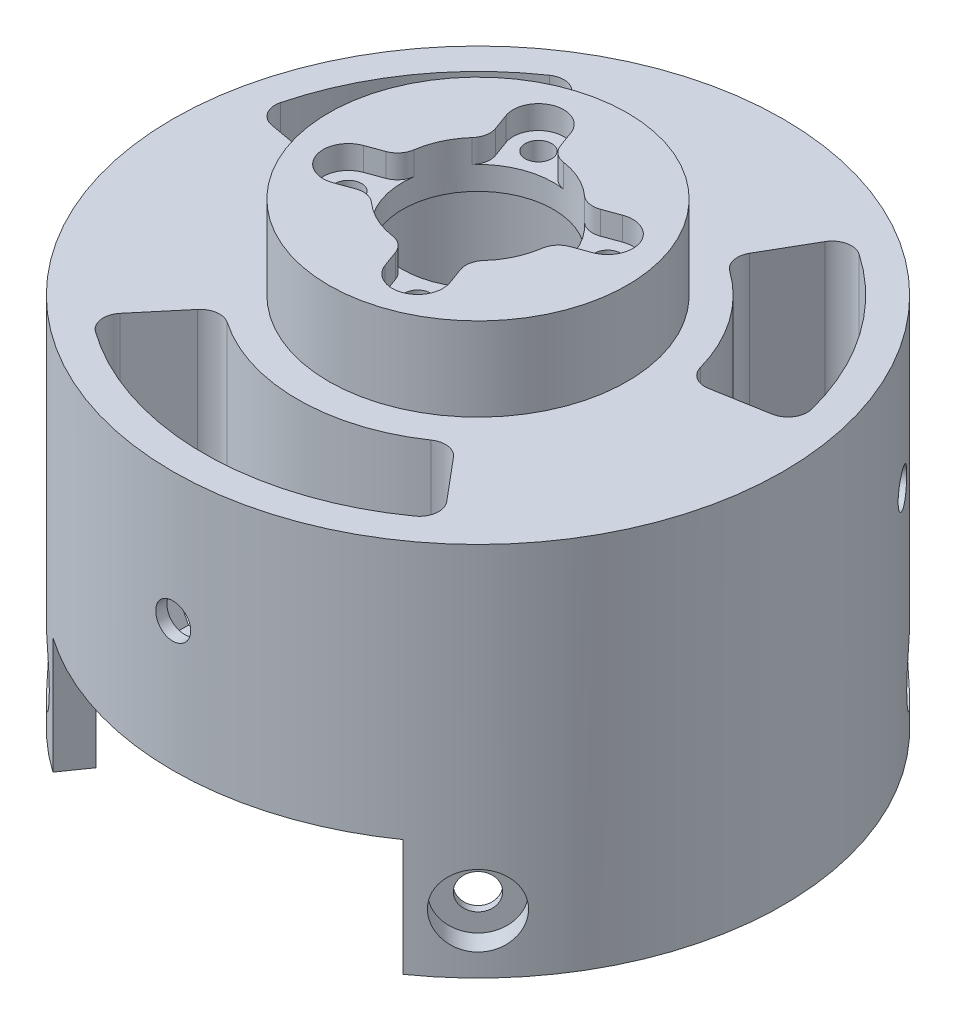
SolidWorks part; units mm, degrees
ref_plane "Front Plane" through (0, 0, 0) normal (0, 0, 1) x (1, 0, 0)
ref_plane "Top Plane" through (0, 0, 0) normal (0, 1, 0) x (1, 0, 0)
ref_plane "Right Plane" through (0, 0, 0) normal (1, 0, 0) x (0, 0, -1)
sketch "Sketch1" plane through (0, 0, 0) normal (0, 1, 0) x (1, 0, 0)
  line L0 (-29.85, 23.9174) -> (-29.85, -23.9174)
  line L1 (29.85, 23.9174) -> (29.85, -23.9174)
  line L2 (-29.85, 0) -> (29.85, 0) construction
  arc A0 (-29.85, -23.9174) -> (29.85, -23.9174) centre (0, 0) ccw
  arc A1 (29.85, 23.9174) -> (-29.85, 23.9174) centre (0, 0) ccw
  point P9 (0, 0)
  dimension "D1" = 59.7
  dimension "D2" = 76.5
extrude "Boss-Extrude1" add sketch "Sketch1" along normal blind 44
sketch "Sketch2" plane through (0, 44, 0) normal (0, 1, 0) x (1, 0, 0)
  line L0 (-4.4463, 12.216) -> (0, 0) construction
  line L1 (0, 13) -> (0, 0) construction
  circle A0 centre (0, 0) radius 13
  point P3 (-4.4463, 12.216)
  dimension "D1" = 26
  dimension "D2" = 20
hole_wizard "CBORE for M3 SHCS1" positions "Sketch2" profile "Sketch3" counterbore size "M3" standard "ANSI Metric" end condition through all
sketch "Sketch3" plane through (-4.4463, 44, -12.216) normal (1, 0, 0) x (0, 0, 1)
  line L0 (0, 0) -> (0, 44)
  line L1 (0, 44) -> (1.7, 44)
  line L3 (1.7, 44) -> (1.7, 3)
  line L4 (1.7, 3) -> (3.25, 3)
  line L5 (3.25, 3) -> (3.25, 0)
  line L7 (3.25, 0) -> (0, 0)
  line L11 (0, -6.35) -> (0, 107.95) construction
  dimension "Thru Hole Dia." = 3.4
  dimension "Thru Hole Depth" = 44
  dimension "C'Bore Dia." = 6.5
  dimension "C'Bore Depth" = 3
ref_axis "Axis1" through (0, 44, 0) along (0, -1, 0)
pattern_circular "CirPattern1" count 4 over 360 about axis through (0, 44, 0) along (0, -1, 0) of "CBORE for M3 SHCS1"
sketch "Sketch4" plane through (0, 0, 0) normal (0, -1, 0) x (1, 0, 0)
  circle A0 centre (0, 0) radius 16.2
  dimension "D1" = 32.4
extrude "Cut-Extrude1" cut sketch "Sketch4" against normal blind 38
sketch "Sketch5" plane through (0, 44, 0) normal (0, 1, 0) x (1, 0, 0)
  circle A0 centre (0, 0) radius 9.7
extrude "Cut-Extrude2" cut sketch "Sketch5" against normal through all
ref_plane "Plane1" through (0, 0, -38.25) normal (0, 0, -1) x (-1, 0, 0)
sketch "Sketch7" plane through (0, 0, 0) normal (0, -1, 0) x (1, 0, 0)
  line L5 (29.85, 23.9174) -> (29.85, -23.9174)
  line L6 (-29.85, 23.9174) -> (-29.85, -23.9174)
  arc A0 (-29.85, -23.9174) -> (29.85, -23.9174) centre (0, 0) ccw construction
  arc A1 (29.85, 23.9174) -> (-29.85, 23.9174) centre (0, 0) ccw construction
  arc A2 (-29.85, -23.9174) -> (29.85, -23.9174) centre (0, 0) ccw
  arc A3 (29.85, 23.9174) -> (-29.85, 23.9174) centre (0, 0) ccw
  circle A4 centre (0, 0) radius 42.1622
  dimension "D1" = 84.3245
extrude "Boss-Extrude2" add sketch "Sketch7" against normal up to surface (44 mm away) up to face at (0, 44, 9.7)
sketch "Sketch9" plane through (0, 0, 0) normal (1, 0, 0) x (0, 0, -1)
  line L0 (-42.1622, 0) -> (-38.3127, 44)
  line L1 (-38.3127, 44) -> (-42.1622, 44)
  line L2 (-42.1622, 44) -> (-42.1622, 0) construction
  line L3 (-42.1622, 44) -> (-42.1622, 0)
  line L4 (0, 0) -> (0, 44) construction
  line L5 (42.1622, 44) -> (-42.1622, 44) construction
  dimension "D1" = 5
revolve "Cut-Revolve2" cut sketch "Sketch9" angle 360 about L4
sketch "Sketch10" plane through (0, 0, 0) normal (1, 0, 0) x (0, 0, -1)
  line L0 (-19.2, 44) -> (-19.2, 33.2871)
  line L1 (38.3127, 44) -> (-38.3127, 44) construction
  line L2 (-19.2, 33.2871) -> (-39.25, 33.2871)
  line L3 (-38.3127, 44) -> (-42.1622, 0) construction
  line L4 (-39.25, 33.2871) -> (-38.3127, 44)
  line L5 (-38.3127, 44) -> (-19.2, 44)
  line L6 (0, 0) -> (0, 44) construction
  line L10 (-42.1622, 0) -> (42.1622, 0) construction
  line L11 (-16.2, 0) -> (16.2, 0) construction
  line L12 (-16.2, 0) -> (16.2, 0) construction
  line L13 (38.3127, 44) -> (-38.3127, 44) construction
  dimension "D1" = 10.7129
  dimension "D2" = 33.2871
  dimension "D3" = 3
revolve "Cut-Revolve3" cut sketch "Sketch10" angle 360 about L6
sketch "Sketch13" plane through (0, 33.2871, 0) normal (0, 1, 0) x (1, 0, 0)
  line L0 (0, -35.25) -> (0, -39.25) construction
  circle A0 centre (0, 0) radius 35.25
  circle A1 centre (0, 0) radius 19.2 construction
  circle A2 centre (0, 0) radius 19.2
  circle A3 centre (0, 0) radius 39.25 construction
  dimension "D1" = 4
extrude "Cut-Extrude3" cut sketch "Sketch13" against normal through all both and the other way through all
sketch "Sketch16" plane through (0, 0, 0) normal (0, -1, 0) x (1, 0, 0)
  line L0 (0, -35.25) -> (0, -19.2) construction
  line L1 (-17.625, -30.5274) -> (-9.6, -16.6277)
  line L2 (17.625, -30.5274) -> (9.6, -16.6277)
  line L3 (-34.7145, -6.1211) -> (-18.9083, -3.334)
  line L4 (-22.6583, 27.0031) -> (-12.3415, 14.7081)
  line L5 (22.6583, 27.0031) -> (12.3415, 14.7081)
  line L6 (34.7145, -6.1211) -> (18.9083, -3.334)
  line L7 (0, 0) -> (-33.1242, 12.0562) construction
  circle A1 centre (0, 0) radius 35.25 construction
  circle A2 centre (0, 0) radius 19.2 construction
  arc A3 (-9.6, -16.6277) -> (9.6, -16.6277) centre (0, 0) ccw
  arc A4 (-17.625, -30.5274) -> (17.625, -30.5274) centre (0, 0) ccw
  arc A5 (-22.6583, 27.0031) -> (-34.7145, -6.1211) centre (0, 0) ccw
  arc A6 (-12.3415, 14.7081) -> (-18.9083, -3.334) centre (0, 0) ccw
  arc A7 (22.6583, 27.0031) -> (34.7145, -6.1211) centre (0, 0) cw
  arc A8 (12.3415, 14.7081) -> (18.9083, -3.334) centre (0, 0) cw
  point P19 (0, 0)
  dimension "D1" = 16.05
  dimension "D3" = 60
  dimension "D4" = 110
  dimension "D2" = 2
extrude "Boss-Extrude4" add sketch "Sketch16" against normal up to surface (33.2871 mm away) up to face at (0, 33.2871, 35.25)
sketch "Sketch17" plane through (0, 33.2871, 0) normal (0, 1, 0) x (1, 0, 0)
  line L0 (0, -19.2) -> (0, -23.2) construction
  circle A0 centre (0, 0) radius 23.2
  circle A1 centre (0, 0) radius 19.2 construction
  circle A2 centre (0, 0) radius 19.2
  dimension "D1" = 4
extrude "Boss-Extrude5" add sketch "Sketch17" against normal up to surface (33.2871 mm away) up to face at (-21.2567, 0, -14.8841)
fillet "Fillet2" radius 2.5 12 edges at (-14.9127, 16.6435, 17.7722) (-22.6583, 16.6435, 27.0031) (22.6583, 16.6435, 27.0031) (14.9127, 16.6435, 17.7722) (-17.625, 16.6435, -30.5274) (-34.7145, 16.6435, -6.1211) (-22.8475, 16.6435, -4.0286) (-11.6, 16.6435, -20.0918) (34.7145, 16.6435, -6.1211) (17.625, 16.6435, -30.5274) (11.6, 16.6435, -20.0918) (22.8475, 16.6435, -4.0286)
ref_plane "Plane2" through (0, 16.6435, 0) normal (0, -1, 0) x (-1, 0, 0)
sketch "Sketch18" plane through (0, 16.6435, 0) normal (0, -1, 0) x (-1, 0, 0)
  line L0 (0, 0) -> (28.8751, 20.2186) construction
  line L1 (0, 0) -> (-28.8751, 20.2186) construction
  line L2 (0, 0) -> (0, -35.25) construction
  line L3 (0, 0) -> (-10.7822, -33.5605) construction
  line L4 (0, 0) -> (10.7822, -33.5605) construction
  arc A0 (34.1459, 8.7532) -> (19.9039, 29.0929) centre (0, 0) ccw construction
  arc A1 (-19.9039, 29.0929) -> (-34.1459, 8.7532) centre (0, 0) ccw construction
  arc A2 (-20.5308, -28.6539) -> (20.5308, -28.6539) centre (0, 0) ccw construction
  arc A3 (-20.5308, -28.6539) -> (0, -35.25) centre (0, 0) ccw construction
  arc A4 (0, -35.25) -> (20.5308, -28.6539) centre (0, 0) ccw construction
ref_plane "Plane4" through (-28.8751, 16.6435, -20.2186) normal (-0.8192, 0, -0.5736) x (-0.5736, 0, 0.8192)
sketch "Sketch20" plane through (-28.8751, 16.6435, -20.2186) normal (-0.8192, 0, -0.5736) x (-0.5736, 0, 0.8192)
  circle A0 centre (0, 0) radius 2.25
  dimension "D1" = 4.5
extrude "Cut-Extrude5" cut sketch "Sketch20" against normal blind 10 and the other way through all
sketch "Sketch21" plane through (-28.8751, 16.6435, -20.2186) normal (-0.8192, 0, -0.5736) x (-0.5736, 0, 0.8192)
  line L1 (4.0415, 0) -> (2.0207, 3.5)
  line L2 (2.0207, 3.5) -> (-2.0207, 3.5)
  line L3 (-2.0207, 3.5) -> (-4.0415, 0)
  line L4 (-4.0415, 0) -> (-2.0207, -3.5)
  line L5 (-2.0207, -3.5) -> (2.0207, -3.5)
  line L6 (2.0207, -3.5) -> (4.0415, 0)
  circle A0 centre (0, 0) radius 3.5 construction
  dimension "D1" = 4.0415
  dimension "D2" = 7
extrude "Cut-Extrude6" cut sketch "Sketch21" against normal blind 10 and the other way blind 2.5
pattern_circular "CirPattern2" count 3 over 250 about axis through (0, 0, 0) along (0, 1, 0) of "Cut-Extrude5", "Cut-Extrude6"
sketch "Sketch22" plane through (0, 44, 0) normal (0, 1, 0) x (1, 0, 0)
  line L2 (-12.216, -4.4463) -> (12.216, 4.4463) construction
  line L3 (-13.3276, -1.3923) -> (11.1044, 7.5003) construction
  line L4 (-11.1044, -7.5003) -> (13.3276, 1.3923) construction
  line L5 (-4.4463, 12.216) -> (4.4463, -12.216) construction
  line L6 (-1.3923, 13.3276) -> (7.5003, -11.1044) construction
  line L7 (-7.5003, 11.1044) -> (1.3923, -13.3276) construction
  line L8 (-11.1044, -7.5003) -> (-1.9424, -4.1656)
  line L9 (-1.9424, -4.1656) -> (1.3923, -13.3276)
  line L10 (7.5003, -11.1044) -> (4.1656, -1.9424)
  line L11 (4.1656, -1.9424) -> (13.3276, 1.3923)
  line L12 (11.1044, 7.5003) -> (1.9424, 4.1656)
  line L13 (1.9424, 4.1656) -> (-1.3923, 13.3276)
  line L14 (-7.5003, 11.1044) -> (-4.1656, 1.9424)
  line L15 (-4.1656, 1.9424) -> (-13.3276, -1.3923)
  arc A0 (-13.3276, -1.3923) -> (-11.1044, -7.5003) centre (-12.216, -4.4463) ccw
  arc A1 (1.3923, -13.3276) -> (7.5003, -11.1044) centre (4.4463, -12.216) ccw
  arc A2 (13.3276, 1.3923) -> (11.1044, 7.5003) centre (12.216, 4.4463) ccw
  arc A3 (-1.3923, 13.3276) -> (-7.5003, 11.1044) centre (-4.4463, 12.216) ccw
  arc A10 (-13.3276, -1.3923) -> (-11.1044, -7.5003) centre (-12.216, -4.4463) ccw construction
  arc A11 (13.3276, 1.3923) -> (11.1044, 7.5003) centre (12.216, 4.4463) ccw construction
  circle A12 centre (12.216, 4.4463) radius 3.25 construction
  arc A13 (-1.3923, 13.3276) -> (-7.5003, 11.1044) centre (-4.4463, 12.216) ccw construction
  arc A14 (1.3923, -13.3276) -> (7.5003, -11.1044) centre (4.4463, -12.216) ccw construction
  circle A15 centre (4.4463, -12.216) radius 3.25 construction
  point P2 (0, 0)
  point P11 (0, 0)
extrude "temporary_probnably" cut sketch "Sketch22" against normal up to surface (3 mm away) up to face at (-4.4463, 41, -10.516)
fillet "also_probably_temporary" radius 2.5 8 edges at (-9.6997, 42.5, 0.0718) (-7.4766, 42.5, 6.1798) (0.0718, 42.5, 9.6997) (6.1798, 42.5, 7.4766) (9.6997, 42.5, -0.0718) (7.4766, 42.5, -6.1798) (-0.0718, 42.5, -9.6997) (-6.1798, 42.5, -7.4766)
sketch "Sketch24" plane through (0, 0, 0) normal (1, 0, 0) x (0, 0, -1)
  line L0 (39.25, 33.2871) -> (-39.25, 33.2871) construction
  line L1 (-42.1622, 0) -> (42.1622, 0) construction
  line L2 (39.25, 33.2871) -> (-39.25, 33.2871) construction
  line L3 (-42.1622, 0) -> (42.1622, 0) construction
  line L4 (42.1622, 0) -> (44.1622, 0)
  line L5 (39.25, 33.2871) -> (41.25, 33.2871)
  line L6 (39.25, 33.2871) -> (42.1622, 0)
  line L7 (41.25, 33.2871) -> (44.1622, 0)
  line L8 (0, 33.2871) -> (0, 0) construction
  dimension "D1" = 2
revolve "key_1" [suppressed] add sketch "Sketch24" angle 9 about L8 other way angle 9
fillet "key_2" [suppressed] radius 0.5
sketch "Sketch25" plane through (0, 0, 0) normal (0, -1, 0) x (1, 0, 0)
  line L0 (-22.5129, -32.1517) -> (22.5129, 32.1517) construction
  line L1 (22.5129, -32.1517) -> (-22.5129, 32.1517) construction
  line L2 (-20.2186, 28.8751) -> (-22.5129, 32.1517)
  line L3 (-20.2186, -28.8751) -> (-22.5129, -32.1517)
  line L4 (0, 0) -> (0, 39.25) construction
  line L6 (20.2186, 28.8751) -> (22.5129, 32.1517)
  line L7 (20.2186, -28.8751) -> (22.5129, -32.1517)
  arc A1 (-22.5129, 32.1517) -> (-22.5129, -32.1517) centre (0, 0) ccw
  circle A3 centre (0, 0) radius 35.25 construction
  circle A4 centre (0, 0) radius 39.25 construction
  arc A7 (-20.2186, -28.8751) -> (-20.2186, 28.8751) centre (0, 0) cw
  arc A21 (20.2186, -28.8751) -> (20.2186, 28.8751) centre (0, 0) ccw
  arc A22 (22.5129, 32.1517) -> (22.5129, -32.1517) centre (0, 0) cw
  circle A24 centre (0, 0) radius 39.25 construction
  point P14 (0, 35.25)
  point P16 (0, 35.25)
  point P18 (0, 0)
  point P19 (0, 0)
  dimension "D1" = 70
  dimension "D2" = 4
extrude "Boss-Extrude6" add sketch "Sketch25" along normal blind 15
ref_plane "Plane5" through (0, -7.5, 0) normal (0, -1, 0) x (-1, 0, 0)
sketch "Sketch26" plane through (0, -7.5, 0) normal (0, -1, 0) x (-1, 0, 0)
  line L0 (0, 0) -> (39.25, 0) construction
  line L1 (0, 0) -> (27.7539, -27.7539) construction
  arc A0 (22.5129, -32.1517) -> (22.5129, 32.1517) centre (0, 0) ccw construction
  dimension "D1" = 45
ref_plane "Plane6" through (-27.7539, -7.5, 27.7539) normal (-0.7071, 0, 0.7071) x (0.7071, 0, 0.7071)
sketch "Sketch28" plane through (-27.7539, -7.5, 27.7539) normal (-0.7071, 0, 0.7071) x (0.7071, 0, 0.7071)
  circle A0 centre (0, 0) radius 2.25
  dimension "D1" = 4.5
extrude "Cut-Extrude7" cut sketch "Sketch28" along normal through all and the other way up to surface other way up to face at (0, 6.9861, -1.1089)
sketch "Sketch29" plane through (-27.7539, -7.5, 27.7539) normal (-0.7071, 0, 0.7071) x (0.7071, 0, 0.7071)
  circle A0 centre (0, 0) radius 2.25 construction
  circle A1 centre (0, 0) radius 2.25
  circle A2 centre (0, 0) radius 4.6
  dimension "D1" = 9.2
extrude "Cut-Extrude8" cut sketch "Sketch29" against normal blind 3
mirror "Mirror1" about plane through (0, 0, 0) normal (0, 0, 1) of "Cut-Extrude8", "Cut-Extrude7"
mirror "Mirror2" about plane through (0, 0, 0) normal (1, 0, 0) of "Mirror1"
sketch "Sketch31" plane through (0, 33.2871, 0) normal (0, 1, 0) x (1, 0, 0)
  circle A1 centre (0, 0) radius 39.25
  circle A2 centre (0, 0) radius 39.25
  dimension "D1" = 0
extrude "Cut-Extrude9" cut sketch "Sketch31" against normal through all flip side to cut
